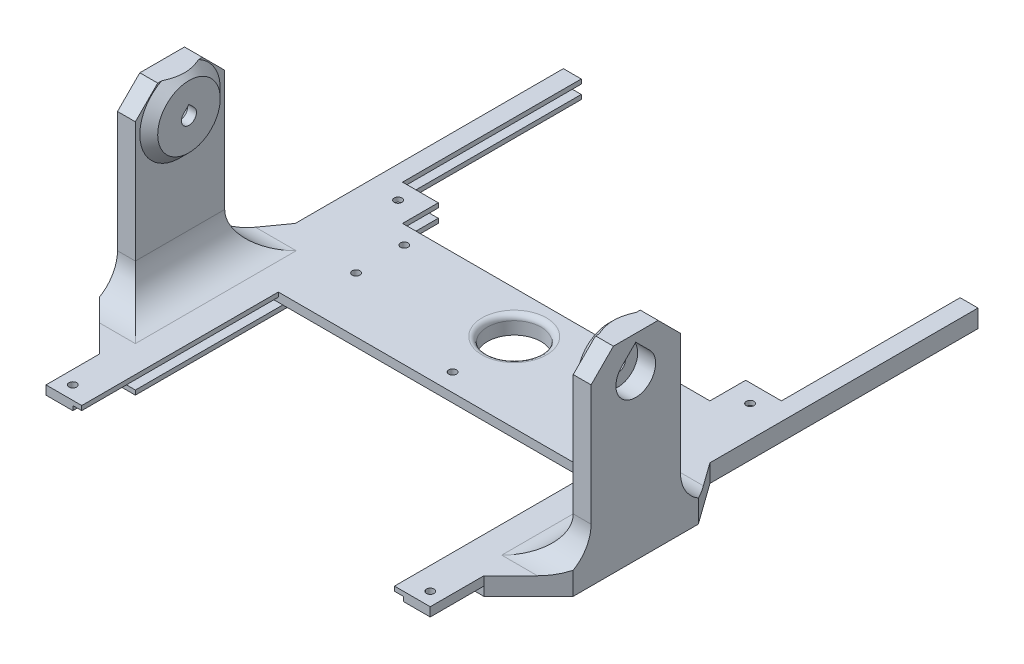
SolidWorks part; units mm, degrees
ref_plane "Alzado" through (0, 0, 0) normal (0, 0, 1) x (1, 0, 0)
ref_plane "Planta" through (0, 0, 0) normal (0, 1, 0) x (1, 0, 0)
ref_plane "Vista lateral" through (0, 0, 0) normal (1, 0, 0) x (0, 0, -1)
sketch "Croquis1" plane through (0, 0, 0) normal (0, 1, 0) x (1, 0, 0)
  line L0 (116, 58) -> (132.5, 35)
  line L8 (116, 88) -> (116, 58)
  line L12 (-132.5, 35) -> (-132.5, -35)
  line L18 (-107.5, -60) -> (-132.5, -35)
  line L22 (-116, 88) -> (-116, 58)
  line L23 (-116, 58) -> (-132.5, 35)
  line L552 (107.5, -60) -> (132.5, -35)
  line L553 (132.5, 35) -> (132.5, -35)
  line L554 (0, 0) -> (0, -155) construction
  line L558 (-80, -60) -> (0, -60) construction
  line L559 (0, -60) -> (80, -60) construction
  line L566 (-132.5, 0) -> (0, 0) construction
  line L567 (0, 0) -> (132.5, 0) construction
  line L569 (0, 101) -> (0, 0) construction
  line L570 (-116, 88) -> (116, 88)
  line L572 (-92.5, -90) -> (-92.5, 40)
  line L573 (-92.5, 40) -> (92.5, 40)
  line L574 (92.5, 40) -> (92.5, -90)
  line L577 (-107.5, -60) -> (-107.5, -90)
  line L578 (-107.5, -90) -> (-92.5, -90)
  line L579 (107.5, -60) -> (107.5, -90)
  line L580 (107.5, -90) -> (92.5, -90)
  point P16 (-132.5, 0)
  dimension "D8" = 25
  dimension "D2" = 232
  dimension "D4" = 30
  dimension "D5" = 30
  dimension "D6" = 130
  dimension "D7" = 23
  dimension "D9" = 25
  dimension "D10" = 15
  dimension "D16" = 265
  dimension "D30" = 70
extrude "Saliente-Extruir2" add sketch "Croquis1" along normal blind 10
sketch "Croquis3" plane through (0, 10, 0) normal (0, 1, 0) x (1, 0, 0)
  line L0 (132.5, 25) -> (122.5, 25)
  line L1 (132.5, -35) -> (132.5, 35) construction
  line L2 (122.5, 25) -> (122.5, -25)
  line L3 (122.5, -25) -> (132.5, -25)
  line L4 (132.5, -25) -> (132.5, 25)
  line L5 (132.5, 35) -> (132.5, 25) construction
  line L6 (132.5, -25) -> (132.5, -35) construction
  line L7 (0, -155) -> (0, -12.7186) construction
  line L10 (0, -135.114) -> (0, 15) construction
  line L11 (0, 64.5) -> (0, -38.3443) construction
  line L12 (-122.5, -25) -> (-132.5, -25)
  line L13 (-122.5, 25) -> (-122.5, -25)
  line L14 (-132.5, 25) -> (-122.5, 25)
  line L15 (-132.5, -25) -> (-132.5, 25)
  dimension "D1" = 10
  dimension "D2" = 50
extrude "Saliente-Extruir4" add sketch "Croquis3" along normal blind 100
sketch "Croquis4" plane through (132.5, 0, 0) normal (1, 0, 0) x (0, 0, -1)
  line L0 (0, 110) -> (0, 90) construction
  line L1 (-25, 110) -> (25, 110) construction
  line L2 (-7.8489, 97.8489) -> (0, 105.6978)
  line L3 (0, 105.6978) -> (7.8489, 97.8489)
  arc A0 (-7.8489, 97.8489) -> (7.8489, 97.8489) centre (0, 90) ccw
  dimension "D1" = 22.2
  dimension "D2" = 20
  dimension "D3" = 90
extrude "Cortar-Extruir1" cut sketch "Croquis4" against normal through all both and the other way through all
sketch "Croquis5" plane through (122.5, 0, 0) normal (-1, 0, 0) x (0, 0, 1)
  line L0 (0, 90) -> (0, 95.9397) construction
  line L1 (-2.9698, 92.9698) -> (0, 95.9397)
  line L2 (0, 95.9397) -> (2.9698, 92.9698)
  circle A0 centre (0, 90) radius 17.5
  arc A1 (-2.9698, 92.9698) -> (2.9698, 92.9698) centre (0, 90) ccw
  dimension "D1" = 8.4
  dimension "D2" = 35
  dimension "D3" = 90
extrude "Saliente-Extruir5" add sketch "Croquis5" along normal blind 5
chamfer "Chaflán1" distance 5 angle 45 1 edges at (122.5, 90, -17.5)
sketch "Croquis6" plane through (-122.5, 0, 0) normal (1, 0, 0) x (0, 0, -1)
  line L0 (0, 90) -> (0, 95.9397) construction
  line L1 (-2.9698, 92.9698) -> (0, 95.9397)
  line L2 (0, 95.9397) -> (2.9699, 92.9698)
  arc A0 (-2.9698, 92.9698) -> (2.9699, 92.9698) centre (0, 90) ccw
  circle A1 centre (0, 90) radius 17.5
  dimension "D1" = 35
  dimension "D2" = 8.4
  dimension "D3" = 90
extrude "Saliente-Extruir6" add sketch "Croquis6" along normal blind 5
chamfer "Chaflán3" distance 12.5 angle 45 4 edges at (-127.5, 110, -25) (-127.5, 110, 25) (127.5, 110, -25) (127.5, 110, 25)
chamfer "Chaflán2" distance 5 angle 45 1 edges at (-122.5, 90, 17.5)
sketch "Croquis8" plane through (-117.5, 0, 0) normal (1, 0, 0) x (0, 0, -1)
  line L1 (-7.5, 97.5) -> (7.5, 97.5)
  line L2 (-7.5, 97.5) -> (-7.5, 82.5)
  line L3 (-7.5, 82.5) -> (7.5, 82.5)
  line L4 (7.5, 97.5) -> (7.5, 82.5)
  line L5 (-7.5, 97.5) -> (7.5, 82.5) construction
  line L6 (-7.5, 82.5) -> (7.5, 97.5) construction
  circle A0 centre (0, 90) radius 4.2
  dimension "D2" = 8.4
  dimension "D1" = 15
extrude "Cortar-Extruir3" [suppressed] cut sketch "Croquis8" against normal blind 2.5
fillet "Redondeo1" radius 20 6 edges at (-127.5, 10, -25) (-127.5, 10, 25) (-122.5, 10, 0) (122.5, 10, 0) (127.5, 10, -25) (127.5, 10, 25)
sketch "Croquis14" plane through (0, 0, -88) normal (0, 0, -1) x (-1, 0, 0)
  line L0 (-86, 10) -> (-116, 10)
  line L1 (-116, 10) -> (-116, 0)
  line L2 (-116, 0) -> (-86, 0)
  line L3 (-116, 0) -> (116, 0) construction
  line L4 (-86, 0) -> (-86, 2.5)
  line L5 (-86, 2.5) -> (-111, 2.5)
  line L6 (-111, 2.5) -> (-111, 7.5)
  line L7 (-111, 7.5) -> (-86, 7.5)
  line L8 (-86, 7.5) -> (-86, 10)
  line L9 (0, 0) -> (0, 10) construction
  line L10 (-116, 10) -> (116, 10) construction
  line L11 (111, 7.5) -> (86, 7.5)
  line L12 (111, 2.5) -> (111, 7.5)
  line L13 (86, 2.5) -> (111, 2.5)
  line L14 (86, 0) -> (86, 2.5)
  line L15 (116, 0) -> (86, 0)
  line L16 (116, 10) -> (116, 0)
  line L17 (86, 10) -> (116, 10)
  line L18 (86, 7.5) -> (86, 10)
  dimension "D1" = 30
  dimension "D2" = 5
  dimension "D3" = 2.5
extrude "Saliente-Extruir9" add sketch "Croquis14" along normal blind 20
sketch "Croquis7" plane through (117.5, 0, 0) normal (-1, 0, 0) x (0, 0, 1)
  line L1 (-7.5, 97.5) -> (7.5, 97.5)
  line L2 (-7.5, 97.5) -> (-7.5, 82.5)
  line L3 (-7.5, 82.5) -> (7.5, 82.5)
  line L4 (7.5, 97.5) -> (7.5, 82.5)
  line L5 (-7.5, 97.5) -> (7.5, 82.5) construction
  line L6 (-7.5, 82.5) -> (7.5, 97.5) construction
  circle A0 centre (0, 90) radius 4.2
  dimension "D2" = 8.4
  dimension "D1" = 15
extrude "Cortar-Extruir2" [suppressed] cut sketch "Croquis7" against normal blind 2.5
sketch "Croquis9" plane through (0, 10, 0) normal (0, 1, 0) x (1, 0, 0)
  line L0 (0, 0) -> (0, 64.5) construction
  line L1 (0, 64.5) -> (0, 88) construction
  line L2 (86, 88) -> (-86, 88) construction
  line L3 (0, 78) -> (-75, 78) construction
  line L4 (-75, 78) -> (-75, 88) construction
  line L5 (0, 64.5) -> (-49.1848, 64.5) construction
  line L6 (100, -90) -> (100, -75) construction
  line L7 (92.5, -90) -> (107.5, -90) construction
  line L8 (86, 98) -> (111, 98) construction
  line L9 (86, 108) -> (86, 88) construction
  circle A0 centre (0, 64.5) radius 15
  circle A1 centre (-75, 78) radius 2.15
  circle A2 centre (75, 78) radius 2.15
  circle A3 centre (75, 51) radius 2.15
  circle A4 centre (-75, 51) radius 2.15
  circle A5 centre (100, -82.5) radius 2.15
  circle A6 centre (-100, -82.5) radius 2.15
  circle A7 centre (98.5, 98) radius 2.15
  circle A8 centre (-98.5, 98) radius 2.15
  dimension "D3" = 30
  dimension "D6" = 4.3
  dimension "D8" = 4.3
  dimension "D10" = 4.3
  dimension "D1" = 64.5
  dimension "D2" = 23.5
  dimension "D4" = 13.5
  dimension "D5" = 75
  dimension "D7" = 15
  dimension "D9" = 25
extrude "Cortar-Extruir4" cut sketch "Croquis9" against normal blind 10
fillet "Redondeo2" radius 3 1 edges at (0, 10, -49.5)
sketch "Croquis11" plane through (0, 10, 0) normal (0, 1, 0) x (1, 0, 0)
  line L1 (-92.5, 40) -> (92.5, 40)
  line L8 (-92.5, 40) -> (-92.5, 20)
  line L9 (-92.5, -90) -> (-92.5, 40) construction
  line L10 (-92.5, 20) -> (92.5, 20)
  line L11 (92.5, 40) -> (92.5, -90) construction
  line L12 (92.5, 20) -> (92.5, 40)
  line L13 (0, 20) -> (0, 40) construction
  circle A0 centre (0, 30) radius 2.15
  dimension "D2" = 4.3
  dimension "D1" = 20
extrude "Saliente-Extruir7" add sketch "Croquis11" against normal blind 5
sketch "Croquis12" plane through (0, 0, 90) normal (0, 0, 1) x (1, 0, 0)
  line L0 (-92.5, 10) -> (-87.5, 10)
  line L1 (-92.5, 10) -> (92.5, 10) construction
  line L2 (-87.5, 10) -> (-87.5, 7.5)
  line L3 (-87.5, 7.5) -> (-92.5, 7.5)
  line L4 (-92.5, 5) -> (-92.5, 10) construction
  line L5 (-92.5, 7.5) -> (-92.5, 5) construction
  line L6 (-92.5, 10) -> (-92.5, 0) construction
  line L7 (-92.5, 2.5) -> (-87.5, 2.5)
  line L8 (-87.5, 2.5) -> (-87.5, 0)
  line L9 (-92.5, 0) -> (92.5, 0) construction
  line L10 (-87.5, 0) -> (-92.5, 0)
  line L11 (-92.5, 0) -> (-92.5, 2.5)
  line L12 (-92.5, 5) -> (-92.5, 2.5) construction
  line L13 (-92.5, 10) -> (-92.5, 7.5)
  line L14 (0, 0) -> (0, 23.8317) construction
  line L15 (92.5, 0) -> (92.5, 2.5)
  line L16 (87.5, 0) -> (92.5, 0)
  line L17 (87.5, 2.5) -> (87.5, 0)
  line L18 (92.5, 2.5) -> (87.5, 2.5)
  line L19 (92.5, 10) -> (87.5, 10)
  line L20 (87.5, 10) -> (87.5, 7.5)
  line L21 (87.5, 7.5) -> (92.5, 7.5)
  line L22 (92.5, 10) -> (92.5, 7.5)
  dimension "D1" = 2.5
  dimension "D2" = 5
extrude "Saliente-Extruir8" add sketch "Croquis12" against normal up to surface (130 mm away) up to face at (0, 2.5, -40)
sketch "Croquis13" plane through (0, 0, 90) normal (0, 0, 1) x (1, 0, 0)
  line L0 (-92.5, 5) -> (-107.5, 5)
  line L1 (-92.5, 7.5) -> (-92.5, 2.5) construction
  line L2 (-107.5, 10) -> (-107.5, 0) construction
  line L3 (-107.5, 5) -> (-107.5, 0)
  line L4 (-107.5, 0) -> (-87.5, 0)
  line L5 (-87.5, 0) -> (-87.5, 5)
  line L6 (-92.5, 5) -> (92.5, 5) construction
  line L7 (-87.5, 5) -> (-92.5, 5)
  line L8 (0, 0) -> (0, 28.3473) construction
  line L9 (87.5, 0) -> (87.5, 5)
  line L10 (107.5, 0) -> (87.5, 0)
  line L11 (107.5, 5) -> (107.5, 0)
  line L12 (92.5, 5) -> (107.5, 5)
  line L13 (87.5, 5) -> (92.5, 5)
extrude "Cortar-Extruir5" cut sketch "Croquis13" against normal blind 30
sketch "Croquis15" plane through (0, 0, -108) normal (0, 0, -1) x (-1, 0, 0)
  line L0 (-106, 2.5) -> (-111, 2.5)
  line L1 (-86, 2.5) -> (-111, 2.5) construction
  line L2 (-111, 2.5) -> (-111, 7.5)
  line L3 (-111, 7.5) -> (-106, 7.5)
  line L4 (-111, 7.5) -> (-86, 7.5) construction
  line L5 (-106, 7.5) -> (-106, 10)
  line L6 (-86, 10) -> (-116, 10) construction
  line L7 (-106, 10) -> (-116, 10)
  line L8 (-116, 10) -> (-116, 0)
  line L9 (-116, 0) -> (-106, 0)
  line L10 (-116, 0) -> (-86, 0) construction
  line L11 (-106, 0) -> (-106, 2.5)
  line L12 (0, 0) -> (0, 6.7597) construction
  line L13 (116, 0) -> (106, 0)
  line L14 (116, 10) -> (116, 0)
  line L15 (106, 10) -> (116, 10)
  line L16 (106, 7.5) -> (106, 10)
  line L17 (111, 7.5) -> (106, 7.5)
  line L18 (111, 2.5) -> (111, 7.5)
  line L19 (106, 2.5) -> (111, 2.5)
  line L20 (106, 0) -> (106, 2.5)
  point P31 (0, 0)
  dimension "D1" = 5
  dimension "D2" = 5
extrude "Saliente-Extruir10" add sketch "Croquis15" along normal blind 100
